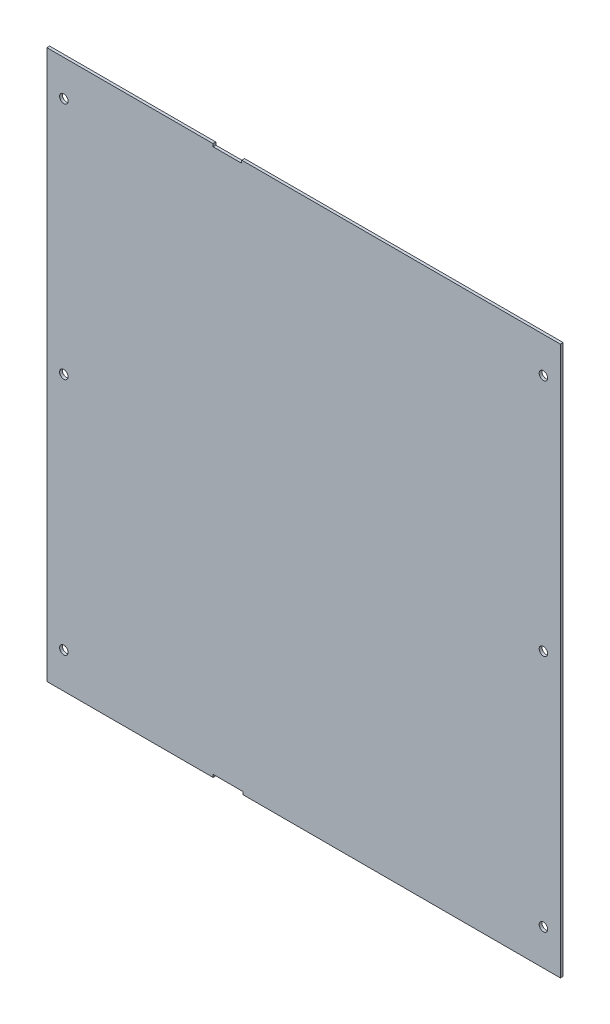
SolidWorks part; units mm, degrees
ref_plane "Front Plane" through (0, 0, 0) normal (0, 0, 1) x (1, 0, 0)
ref_plane "Top Plane" through (0, 0, 0) normal (0, 1, 0) x (1, 0, 0)
ref_plane "Right Plane" through (0, 0, 0) normal (1, 0, 0) x (0, 0, -1)
sketch "Sketch2" plane through (0, 0, 0) normal (0, 0, 1) x (1, 0, 0)
  line L0 (-66.4, 201.34) -> (-66.4, 199.34)
  line L1 (-188.4, 201.34) -> (-66.4, 201.34)
  line L2 (-188.4, 201.34) -> (-188.4, -201.34)
  line L3 (-188.4, -201.34) -> (-66.4, -201.34)
  line L4 (188.4, 201.34) -> (188.4, -201.34)
  line L5 (-188.4, 201.34) -> (188.4, -201.34) construction
  line L6 (-188.4, -201.34) -> (188.4, 201.34) construction
  line L7 (-66.4, 199.34) -> (-45.4, 199.34)
  line L8 (-45.4, 199.34) -> (-45.4, 201.34)
  line L9 (-45.4, 201.34) -> (188.4, 201.34)
  line L10 (-44.4, -201.34) -> (-44.4, -199.34)
  line L11 (-44.4, -199.34) -> (-66.4, -199.34)
  line L12 (-66.4, -199.34) -> (-66.4, -201.34)
  line L13 (-44.4, -201.34) -> (188.4, -201.34)
  point P0 (0, 0)
  dimension "D1" = 2
  dimension "Length 1" = 376.8
  dimension "D2" = 122
  dimension "Length 2" = 402.68
  dimension "D3" = 143
  dimension "D4" = 122
  dimension "D5" = 144
  dimension "D6" = 2
extrude "Boss-Extrude1" add sketch "Sketch2" along normal blind 2.032
sketch "Sketch3" [suppressed] plane through (0, 0, 2.032) normal (0, 0, 1) x (1, 0, 0)
  circle A0 centre (-175.117, 128.01) radius 3.1
  circle A1 centre (175.117, 128.01) radius 3.1
  circle A8 centre (-175.1171, -128.01) radius 3.1
  circle A9 centre (175.1169, -128.01) radius 3.1
  dimension "D1" = 6.2
extrude "Cut-Extrude1" [suppressed] cut sketch "Sketch3" against normal through all both and the other way through all
fillet "Fillet1" [suppressed] radius 10
sketch "Sketch4" [suppressed] plane through (0, 0, 0) normal (0, 0, -1) x (-1, 0, 0)
  circle A0 centre (-423.777, 128.01) radius 3.1
  circle A1 centre (423.777, 128.01) radius 3.1
  circle A2 centre (423.777, -128.01) radius 3.1
  circle A3 centre (-423.777, -128.01) radius 3.1
  dimension "D1" = 6.2
extrude "Cut-Extrude2" [suppressed] cut sketch "Sketch4" against normal through all both and the other way through all
sketch "Sketch5" [suppressed] plane through (0, 0, 0) normal (0, 0, -1) x (-1, 0, 0)
  circle A0 centre (-175.117, -437.5) radius 3.1
  circle A1 centre (175.1169, -437.5) radius 3.1
  circle A2 centre (175.1169, 437.5) radius 3.1
  circle A3 centre (-175.117, 437.5) radius 3.1
  dimension "D1" = 6.2
extrude "Cut-Extrude3" [suppressed] cut sketch "Sketch5" against normal through all both and the other way through all
fillet "Fillet3" [suppressed] radius 10
sketch "Sketch6" plane through (0, 0, 0) normal (0, 0, -1) x (-1, 0, 0)
  circle A0 centre (175.9, -175.117) radius 3.1
  circle A1 centre (175.9, 175.117) radius 3.1
  circle A2 centre (-175.9, 175.117) radius 3.1
  circle A3 centre (-175.9, -175.117) radius 3.1
  circle A5 centre (-175.9, 0) radius 3.1
  circle A6 centre (175.9, 0) radius 3.1
  dimension "D1" = 6.2
  dimension "D2" = 6.2
  dimension "D3" = 6.2
fillet "Fillet5" [suppressed] radius 10
extrude "Cut-Extrude4" cut sketch "Sketch6" against normal through all both and the other way through all
sketch "Sketch7" [suppressed] plane through (0, 0, 2.032) normal (0, 0, 1) x (1, 0, 0)
  circle A0 centre (-139.6, -129.6148) radius 3.1
  circle A1 centre (-139.6, 138.5552) radius 3.1
  circle A2 centre (139.6, 151.166) radius 3.1
  circle A3 centre (139.6, -129.36) radius 3.1
  dimension "D1" = 6.2
extrude "Cut-Extrude5" [suppressed] cut sketch "Sketch7" against normal through all both and the other way through all
fillet "Fillet4" [suppressed] radius 10
sketch "Sketch8" [suppressed] plane through (0, 0, 2.032) normal (0, 0, 1) x (1, 0, 0)
  line L0 (-37.3761, -47.01) -> (-37.3761, -22.01) construction
  line L1 (32.5, -51.886) -> (-32.5, -51.886) construction
  line L2 (37.376, -22.01) -> (37.376, -47.01) construction
  line L3 (-32.5, -17.1339) -> (32.5, -17.1339) construction
  line L4 (-37.3761, -47.01) -> (-37.3761, -22.01) construction
  line L5 (32.5, -51.886) -> (-32.5, -51.886) construction
  line L6 (37.376, -22.01) -> (37.376, -47.01) construction
  line L7 (-32.5, -17.1339) -> (32.5, -17.1339) construction
  line L8 (-37.6761, -47.01) -> (-37.6761, -22.01)
  line L9 (32.5, -52.186) -> (-32.5, -52.186)
  line L10 (37.676, -22.01) -> (37.676, -47.01)
  line L11 (-32.5, -16.8339) -> (32.5, -16.8339)
  arc A0 (-37.3761, -47.01) -> (-32.5, -51.886) centre (-32.5, -47.01) ccw construction
  arc A1 (32.5, -51.886) -> (37.376, -47.01) centre (32.5, -47.01) ccw construction
  arc A2 (37.376, -22.01) -> (32.5, -17.1339) centre (32.5, -22.01) ccw construction
  arc A3 (-32.5, -17.1339) -> (-37.3761, -22.01) centre (-32.5, -22.01) ccw construction
  arc A4 (-37.3761, -47.01) -> (-32.5, -51.886) centre (-32.5, -47.01) ccw construction
  arc A5 (32.5, -51.886) -> (37.376, -47.01) centre (32.5, -47.01) ccw construction
  arc A6 (37.376, -22.01) -> (32.5, -17.1339) centre (32.5, -22.01) ccw construction
  arc A7 (-32.5, -17.1339) -> (-37.3761, -22.01) centre (-32.5, -22.01) ccw construction
  arc A8 (-32.5, -16.8339) -> (-37.6761, -22.01) centre (-32.5, -22.01) ccw
  arc A9 (-37.6761, -47.01) -> (-32.5, -52.186) centre (-32.5, -47.01) ccw
  arc A10 (32.5, -52.186) -> (37.676, -47.01) centre (32.5, -47.01) ccw
  arc A11 (37.676, -22.01) -> (32.5, -16.8339) centre (32.5, -22.01) ccw
  dimension "D1" = 0.3
extrude "Cut-Extrude6" [suppressed] cut sketch "Sketch8" against normal through all
sketch "Sketch9" [suppressed] plane through (0, 0, 2.032) normal (0, 0, 1) x (1, 0, 0)
  line L0 (-51.9979, -76.9078) -> (-51.9979, -83.1078) construction
  line L1 (-48.8979, -76.9078) -> (-48.8979, -83.1078)
  line L2 (-55.0979, -76.9078) -> (-55.0979, -83.1078)
  line L3 (51.9978, -76.9078) -> (51.9978, -83.1078) construction
  line L4 (55.0978, -76.9078) -> (55.0978, -83.1078)
  line L5 (48.8978, -76.9078) -> (48.8978, -83.1078)
  circle A0 centre (-51.9979, -1.5121) radius 3.1
  circle A1 centre (51.9978, -1.5121) radius 3.1
  circle A2 centre (-51.9979, -80.0078) radius 3.1 construction
  arc A3 (-48.8979, -76.9078) -> (-55.0979, -76.9078) centre (-51.9979, -76.9078) ccw
  arc A4 (-55.0979, -83.1078) -> (-48.8979, -83.1078) centre (-51.9979, -83.1078) ccw
  circle A5 centre (51.9978, -80.0078) radius 3.1 construction
  arc A6 (55.0978, -76.9078) -> (48.8978, -76.9078) centre (51.9978, -76.9078) ccw
  arc A7 (48.8978, -83.1078) -> (55.0978, -83.1078) centre (51.9978, -83.1078) ccw
  point P11 (-51.9979, -80.0078)
  point P17 (51.9978, -80.0078)
  dimension "D1" = 6.2
extrude "Cut-Extrude7" [suppressed] cut sketch "Sketch9" against normal through all
sketch "Sketch10" [suppressed] plane through (0, 0, 2.032) normal (0, 0, 1) x (1, 0, 0)
  line L0 (90, 90.8143) -> (-90, 90.8143) construction
  line L1 (75.5, 121.0648) -> (-75.5, 121.0648) construction
  line L2 (75.5, 90.8143) -> (-75.5, 90.8143) construction
  line L3 (75.5, 121.0648) -> (-75.5, 121.0648) construction
  line L4 (75.5, 90.5143) -> (-75.5, 90.5143)
  line L5 (75.5, 121.3648) -> (-75.5, 121.3648)
  spline S0 degree 3 poles (3074.5134, 128.3274) (69.9947, 120.8875) (74.4296, 121.0676) (75.5298, 121.0647) (75.5326, 121.0647) (75.6464, 121.0643) (75.8632, 121.0597) (76.1642, 121.0437) (76.381, 121.0257) (76.5878, 121.0048) (76.7942, 120.9803) (77.0603, 120.9413) (77.3248, 120.8952) (77.5598, 120.8477) (77.7949, 120.7947) (77.9818, 120.7481) (78.1109, 120.7132) (78.2822, 120.6658) (78.5457, 120.5872) (78.9382, 120.4526) (79.2301, 120.3392) (79.3912, 120.2721) (79.5867, 120.1894) (79.8287, 120.0797) (80.0659, 119.9615) (80.3074, 119.8374) (80.4668, 119.7503) (80.8016, 119.5566) (81.1538, 119.3396) (81.5223, 119.0841) (81.7178, 118.9395) (81.8836, 118.8158) (82.0678, 118.6719) (82.2476, 118.5231) (82.4279, 118.3716) (82.5907, 118.2288) (82.7493, 118.0824) (82.9322, 117.9119) (83.2327, 117.6176) (83.6639, 117.1527) (83.9602, 116.8013) (84.1153, 116.6069) (84.2773, 116.4024) (84.4141, 116.2207) (84.6783, 115.8519) (84.9333, 115.4777) (85.2917, 114.8964) (85.6175, 114.311) (85.8168, 113.9147) (86.0153, 113.4997) (86.199, 113.0919) (86.3667, 112.6759) (86.5131, 112.2932) (86.6057, 112.0372) (86.6922, 111.7793) (86.7672, 111.5516) (86.8201, 111.3823) (86.9423, 110.9692) (87.0765, 110.4773) (87.247, 109.7286) (87.3625, 109.1005) (87.4598, 108.4609) (87.5282, 107.8937) (87.5661, 107.4468) (87.5939, 107.0493) (87.6148, 106.6536) (87.6234, 106.2582) (87.6251, 106.0243) (87.6252, 105.9711) (87.6249, 105.6521) (87.6131, 105.121) (87.5623, 104.3289) (87.4962, 103.7081) (87.4136, 103.0987) (87.3259, 102.565) (87.2377, 102.1278) (87.1497, 101.7237) (87.0462, 101.2874) (86.9261, 100.8539) (86.8399, 100.5642) (86.8173, 100.4902) (86.7193, 100.1763) (86.5601, 99.7025) (86.2936, 99.0104) (86.0691, 98.4959) (85.9353, 98.2118) (85.8046, 97.939) (85.5968, 97.5281) (85.2615, 96.9315) (84.9154, 96.3749) (84.674, 96.0215) (84.4707, 95.7372) (84.3836, 95.6191) (84.1969, 95.3742) (84.0085, 95.1357) (83.8127, 94.9039) (83.5714, 94.6273) (83.2684, 94.2969) (82.801, 93.8368) (82.325, 93.4136) (81.9762, 93.1336) (81.7857, 92.9898) (81.6442, 92.8839) (81.4108, 92.7157) (81.0521, 92.477) (80.7023, 92.2626) (80.4711, 92.1321) (80.188, 91.9784) (79.8408, 91.802) (79.3125, 91.5689) (78.7817, 91.3682) (78.4002, 91.2473) (78.1974, 91.1898) (78.1177, 91.1676) (77.9122, 91.1121) (77.5556, 91.0277) (77.1709, 90.9552) (76.9362, 90.9195) (76.822, 90.9037) (76.7327, 90.8917) (76.589, 90.8744) (76.4218, 90.8572) (76.2707, 90.8443) (76.119, 90.8335) (75.9751, 90.8254) (75.8173, 90.819) (75.6699, 90.8154) (75.5675, 90.8144) (75.515, 90.8143) (75.5096, 90.8143) (74.905, 90.8139) (86.1929, 90.8711) (3073.38, 91.1293) knots -0.002735 -0.002735 -0.002735 -0.002735 0.000024 0.000024 0.000031 0.000031 0.00032 0.000611 0.000881 0.000959 0.001235 0.001516 0.001798 0.002081 0.002271 0.00255 0.002673 0.002673 0.003081 0.003491 0.003902 0.004009 0.004009 0.004534 0.004802 0.004802 0.005346 0.005346 0.00596 0.006584 0.006682 0.006682 0.007198 0.007375 0.007375 0.007897 0.008019 0.008019 0.008644 0.009276 0.009915 0.010016 0.010016 0.010692 0.010692 0.01136 0.012037 0.01273 0.013365 0.013365 0.014106 0.014701 0.014701 0.015325 0.01551 0.01551 0.016038 0.016038 0.016796 0.017562 0.018339 0.018711 0.0195 0.020047 0.020047 0.020686 0.021225 0.021225 0.021384 0.021384 0.022179 0.022975 0.023768 0.024057 0.024824 0.025393 0.025393 0.026061 0.026729 0.026729 0.02696 0.02696 0.027709 0.028454 0.029189 0.029402 0.029402 0.030103 0.030794 0.031468 0.032075 0.032075 0.032512 0.032512 0.032989 0.033412 0.033412 0.03408 0.034748 0.035373 0.035987 0.036085 0.036085 0.036513 0.036938 0.037359 0.037729 0.037729 0.03832 0.038894 0.039463 0.040026 0.040094 0.040094 0.040274 0.04073 0.041182 0.041431 0.041431 0.041522 0.041701 0.041881 0.04206 0.042186 0.042356 0.042495 0.042636 0.042751 0.042751 0.042763 0.042763 0.04424 0.04424 0.04424 0.04424 weights 1 1 1 1 1 1 1 1 1 1 1 1 1 1 1 1 1 1 1 1 1 1 1 1 1 1 1 1 1 1 1 1 1 1 1 1 1 1 1 1 1 1 1 1 1 1 1 1 1 1 1 1 1 1 1 1 1 1 1 1 1 1 1 1 1 1 1 1 1 1 1 1 1 1 1 1 1 1 1 1 1 1 1 1 1 1 1 1 1 1 1 1 1 1 1 1 1 1 1 1 1 1 1 1 1 1 1 1 1 1 1 1 1 1 1 1 1 1 1 1 1 1 1 1 1 1 1 1 1 1 1 1 1 only from (75.5, 121.0648) to (75.5, 90.8143) construction
  spline S1 degree 3 poles (-3073.3122, 91.0618) (-68.1123, 90.8701) (-74.8748, 90.8132) (-75.5178, 90.8143) (-75.5188, 90.8143) (-75.6217, 90.8145) (-75.8102, 90.8179) (-76.0955, 90.831) (-76.3619, 90.851) (-76.5858, 90.8739) (-76.7898, 90.8988) (-76.9915, 90.9272) (-77.2231, 90.9655) (-77.4535, 91.0092) (-77.6838, 91.0585) (-77.9135, 91.1133) (-78.0691, 91.1542) (-78.2957, 91.2169) (-78.5939, 91.3066) (-79.0185, 91.4558) (-79.292, 91.5651) (-79.5791, 91.6863) (-79.8887, 91.8262) (-80.19, 91.98) (-80.431, 92.1099) (-80.5257, 92.1628) (-80.8023, 92.3227) (-81.1645, 92.5459) (-81.531, 92.801) (-81.7204, 92.9414) (-81.86, 93.0454) (-82.1004, 93.2319) (-82.4461, 93.5213) (-82.6659, 93.719) (-82.9234, 93.9587) (-83.2202, 94.2488) (-83.646, 94.7063) (-83.9884, 95.1104) (-84.1878, 95.3632) (-84.3522, 95.5769) (-84.4471, 95.7045) (-84.6398, 95.973) (-84.836, 96.257) (-85.0675, 96.6184) (-85.2256, 96.8798) (-85.2925, 96.9937) (-85.434, 97.2372) (-85.6646, 97.6556) (-85.9851, 98.3049) (-86.2393, 98.8843) (-86.3829, 99.2453) (-86.4494, 99.4187) (-86.55, 99.6841) (-86.6603, 99.9986) (-86.7491, 100.2733) (-86.796, 100.4205) (-86.8377, 100.5557) (-86.8778, 100.6914) (-86.9586, 100.968) (-87.0905, 101.4582) (-87.2577, 102.2029) (-87.3631, 102.7847) (-87.4242, 103.1837) (-87.4447, 103.3291) (-87.4978, 103.7198) (-87.5689, 104.3709) (-87.6172, 105.2208) (-87.6253, 105.7445) (-87.6253, 105.9682) (-87.6252, 105.997) (-87.6239, 106.2925) (-87.6102, 106.8253) (-87.5586, 107.5863) (-87.4824, 108.2948) (-87.3824, 108.9904) (-87.2522, 109.7032) (-87.0975, 110.3876) (-86.9658, 110.8838) (-86.8849, 111.1642) (-86.8565, 111.2593) (-86.8202, 111.38) (-86.7924, 111.4698) (-86.7084, 111.7335) (-86.617, 112.0056) (-86.5018, 112.3221) (-86.4473, 112.4659) (-86.3387, 112.7484) (-86.1745, 113.1489) (-85.9253, 113.6947) (-85.6673, 114.2147) (-85.3669, 114.7671) (-85.0165, 115.3478) (-84.7388, 115.7647) (-84.5819, 115.9866) (-84.4547, 116.1642) (-84.3562, 116.297) (-84.1525, 116.5617) (-83.9899, 116.7652) (-83.8222, 116.9634) (-83.7278, 117.0727) (-83.6931, 117.1124) (-83.512, 117.3171) (-83.2145, 117.6374) (-82.7539, 118.0859) (-82.3108, 118.4763) (-81.9806, 118.7415) (-81.7867, 118.8888) (-81.7261, 118.9339) (-81.5923, 119.0328) (-81.36, 119.1984) (-81.006, 119.4314) (-80.7579, 119.5818) (-80.6329, 119.6543) (-80.5302, 119.7137) (-80.4331, 119.768) (-80.1632, 119.9135) (-79.8189, 120.0873) (-79.2869, 120.3208) (-78.7504, 120.5219) (-78.374, 120.6396) (-78.1216, 120.7105) (-77.9102, 120.7674) (-77.5659, 120.8488) (-77.1858, 120.9214) (-76.9471, 120.958) (-76.8184, 120.9759) (-76.7272, 120.988) (-76.582, 121.0054) (-76.4149, 121.0225) (-76.2649, 121.0352) (-76.1143, 121.0458) (-75.972, 121.0538) (-75.8151, 121.0601) (-75.6689, 121.0637) (-75.5671, 121.0646) (-75.515, 121.0648) (-75.5096, 121.0648) (-74.9079, 121.0651) (-86.2343, 121.0084) (-3073.1531, 120.7526) knots -0.001473 -0.001473 -0.001473 -0.001473 0.000013 0.000013 0.000016 0.000016 0.000262 0.000488 0.000778 0.001021 0.001162 0.001413 0.001666 0.001921 0.002175 0.002427 0.002667 0.002667 0.00313 0.003594 0.004001 0.004001 0.004517 0.00501 0.00501 0.005334 0.005334 0.005966 0.006608 0.006668 0.006668 0.007126 0.007571 0.008002 0.008002 0.008616 0.009237 0.009867 0.010196 0.010196 0.010669 0.010669 0.011178 0.011692 0.011939 0.012084 0.012084 0.012777 0.013509 0.014247 0.014667 0.014667 0.0148 0.015513 0.015656 0.015656 0.015971 0.016076 0.016076 0.016826 0.017586 0.018355 0.018595 0.018795 0.018795 0.019775 0.020751 0.02133 0.02133 0.021415 0.021415 0.022207 0.023001 0.023696 0.024344 0.025112 0.025872 0.026446 0.026646 0.026742 0.026742 0.027021 0.027021 0.027563 0.027871 0.02802 0.02802 0.028771 0.029311 0.029815 0.03051 0.031195 0.031844 0.032003 0.032003 0.032493 0.032493 0.032991 0.033263 0.033263 0.033421 0.033421 0.034077 0.034725 0.035343 0.035843 0.035988 0.036067 0.036067 0.036482 0.036912 0.037319 0.037341 0.037341 0.037673 0.037673 0.038257 0.038828 0.039418 0.039978 0.040009 0.040201 0.04063 0.041056 0.041342 0.041342 0.04144 0.041618 0.041798 0.041977 0.042099 0.042269 0.042405 0.042545 0.04266 0.04266 0.042671 0.042671 0.044141 0.044141 0.044141 0.044141 weights 1 1 1 1 1 1 1 1 1 1 1 1 1 1 1 1 1 1 1 1 1 1 1 1 1 1 1 1 1 1 1 1 1 1 1 1 1 1 1 1 1 1 1 1 1 1 1 1 1 1 1 1 1 1 1 1 1 1 1 1 1 1 1 1 1 1 1 1 1 1 1 1 1 1 1 1 1 1 1 1 1 1 1 1 1 1 1 1 1 1 1 1 1 1 1 1 1 1 1 1 1 1 1 1 1 1 1 1 1 1 1 1 1 1 1 1 1 1 1 1 1 1 1 1 1 1 1 1 1 1 1 1 1 1 1 1 1 1 1 1 only from (-75.5, 90.8143) to (-75.5, 121.0648) construction
  spline S2 degree 3 poles (75.5, 121.0648) (75.5079, 121.0648) (75.5205, 121.0647) (75.5326, 121.0647) (75.6464, 121.0643) (75.8632, 121.0597) (76.1642, 121.0437) (76.381, 121.0257) (76.5878, 121.0048) (76.7942, 120.9803) (77.0603, 120.9413) (77.3248, 120.8952) (77.5598, 120.8477) (77.7949, 120.7947) (77.9818, 120.7481) (78.1109, 120.7132) (78.2822, 120.6658) (78.5457, 120.5872) (78.9382, 120.4526) (79.2301, 120.3392) (79.3912, 120.2721) (79.5867, 120.1894) (79.8287, 120.0797) (80.0659, 119.9615) (80.3074, 119.8374) (80.4668, 119.7503) (80.8016, 119.5566) (81.1538, 119.3396) (81.5223, 119.0841) (81.7178, 118.9395) (81.8836, 118.8158) (82.0678, 118.6719) (82.2476, 118.5231) (82.4279, 118.3716) (82.5907, 118.2288) (82.7493, 118.0824) (82.9322, 117.9119) (83.2327, 117.6176) (83.6639, 117.1527) (83.9602, 116.8013) (84.1153, 116.6069) (84.2773, 116.4024) (84.4141, 116.2207) (84.6783, 115.8519) (84.9333, 115.4777) (85.2917, 114.8964) (85.6175, 114.311) (85.8168, 113.9147) (86.0153, 113.4997) (86.199, 113.0919) (86.3667, 112.6759) (86.5131, 112.2932) (86.6057, 112.0372) (86.6922, 111.7793) (86.7672, 111.5516) (86.8201, 111.3823) (86.9423, 110.9692) (87.0765, 110.4773) (87.247, 109.7286) (87.3625, 109.1005) (87.4598, 108.4609) (87.5282, 107.8937) (87.5661, 107.4468) (87.5939, 107.0493) (87.6148, 106.6536) (87.6234, 106.2582) (87.6251, 106.0243) (87.6252, 105.9711) (87.6249, 105.6521) (87.6131, 105.121) (87.5623, 104.3289) (87.4962, 103.7081) (87.4136, 103.0987) (87.3259, 102.565) (87.2377, 102.1278) (87.1497, 101.7237) (87.0462, 101.2874) (86.9261, 100.8539) (86.8399, 100.5642) (86.8173, 100.4902) (86.7193, 100.1763) (86.5601, 99.7025) (86.2936, 99.0104) (86.0691, 98.4959) (85.9353, 98.2118) (85.8046, 97.939) (85.5968, 97.5281) (85.2615, 96.9315) (84.9154, 96.3749) (84.674, 96.0215) (84.4707, 95.7372) (84.3836, 95.6191) (84.1969, 95.3742) (84.0085, 95.1357) (83.8127, 94.9039) (83.5714, 94.6273) (83.2684, 94.2969) (82.801, 93.8368) (82.325, 93.4136) (81.9762, 93.1336) (81.7857, 92.9898) (81.6442, 92.8839) (81.4108, 92.7157) (81.0521, 92.477) (80.7023, 92.2626) (80.4711, 92.1321) (80.188, 91.9784) (79.8408, 91.802) (79.3125, 91.5689) (78.7817, 91.3682) (78.4002, 91.2473) (78.1974, 91.1898) (78.1177, 91.1676) (77.9122, 91.1121) (77.5556, 91.0277) (77.1709, 90.9552) (76.9362, 90.9195) (76.822, 90.9037) (76.7327, 90.8917) (76.589, 90.8744) (76.4218, 90.8572) (76.2707, 90.8443) (76.119, 90.8335) (75.9751, 90.8254) (75.8173, 90.819) (75.6699, 90.8154) (75.5675, 90.8144) (75.515, 90.8143) (75.5076, 90.8143) (75.5015, 90.8143) (75.5, 90.8143) knots 0 0 0 0 0.000024 0.000031 0.000031 0.00032 0.000611 0.000881 0.000959 0.001235 0.001516 0.001798 0.002081 0.002271 0.00255 0.002673 0.002673 0.003081 0.003491 0.003902 0.004009 0.004009 0.004534 0.004802 0.004802 0.005346 0.005346 0.00596 0.006584 0.006682 0.006682 0.007198 0.007375 0.007375 0.007897 0.008019 0.008019 0.008644 0.009276 0.009915 0.010016 0.010016 0.010692 0.010692 0.01136 0.012037 0.01273 0.013365 0.013365 0.014106 0.014701 0.014701 0.015325 0.01551 0.01551 0.016038 0.016038 0.016796 0.017562 0.018339 0.018711 0.0195 0.020047 0.020047 0.020686 0.021225 0.021225 0.021384 0.021384 0.022179 0.022975 0.023768 0.024057 0.024824 0.025393 0.025393 0.026061 0.026729 0.026729 0.02696 0.02696 0.027709 0.028454 0.029189 0.029402 0.029402 0.030103 0.030794 0.031468 0.032075 0.032075 0.032512 0.032512 0.032989 0.033412 0.033412 0.03408 0.034748 0.035373 0.035987 0.036085 0.036085 0.036513 0.036938 0.037359 0.037729 0.037729 0.03832 0.038894 0.039463 0.040026 0.040094 0.040094 0.040274 0.04073 0.041182 0.041431 0.041431 0.041522 0.041701 0.041881 0.04206 0.042186 0.042356 0.042495 0.042636 0.042751 0.042751 0.042763 0.042767 0.042767 0.042767 0.042767 weights 1 1 1 1 1 1 1 1 1 1 1 1 1 1 1 1 1 1 1 1 1 1 1 1 1 1 1 1 1 1 1 1 1 1 1 1 1 1 1 1 1 1 1 1 1 1 1 1 1 1 1 1 1 1 1 1 1 1 1 1 1 1 1 1 1 1 1 1 1 1 1 1 1 1 1 1 1 1 1 1 1 1 1 1 1 1 1 1 1 1 1 1 1 1 1 1 1 1 1 1 1 1 1 1 1 1 1 1 1 1 1 1 1 1 1 1 1 1 1 1 1 1 1 1 1 1 1 1 1 1 1 construction
  spline S3 degree 3 poles (-75.5, 90.8143) (-75.5046, 90.8143) (-75.512, 90.8143) (-75.5188, 90.8143) (-75.6217, 90.8145) (-75.8102, 90.8179) (-76.0955, 90.831) (-76.3619, 90.851) (-76.5858, 90.8739) (-76.7898, 90.8988) (-76.9915, 90.9272) (-77.2231, 90.9655) (-77.4535, 91.0092) (-77.6838, 91.0585) (-77.9135, 91.1133) (-78.0691, 91.1542) (-78.2957, 91.2169) (-78.5939, 91.3066) (-79.0185, 91.4558) (-79.292, 91.5651) (-79.5791, 91.6863) (-79.8887, 91.8262) (-80.19, 91.98) (-80.431, 92.1099) (-80.5257, 92.1628) (-80.8023, 92.3227) (-81.1645, 92.5459) (-81.531, 92.801) (-81.7204, 92.9414) (-81.86, 93.0454) (-82.1004, 93.2319) (-82.4461, 93.5213) (-82.6659, 93.719) (-82.9234, 93.9587) (-83.2202, 94.2488) (-83.646, 94.7063) (-83.9884, 95.1104) (-84.1878, 95.3632) (-84.3522, 95.5769) (-84.4471, 95.7045) (-84.6398, 95.973) (-84.836, 96.257) (-85.0675, 96.6184) (-85.2256, 96.8798) (-85.2925, 96.9937) (-85.434, 97.2372) (-85.6646, 97.6556) (-85.9851, 98.3049) (-86.2393, 98.8843) (-86.3829, 99.2453) (-86.4494, 99.4187) (-86.55, 99.6841) (-86.6603, 99.9986) (-86.7491, 100.2733) (-86.796, 100.4205) (-86.8377, 100.5557) (-86.8778, 100.6914) (-86.9586, 100.968) (-87.0905, 101.4582) (-87.2577, 102.2029) (-87.3631, 102.7847) (-87.4242, 103.1837) (-87.4447, 103.3291) (-87.4978, 103.7198) (-87.5689, 104.3709) (-87.6172, 105.2208) (-87.6253, 105.7445) (-87.6253, 105.9682) (-87.6252, 105.997) (-87.6239, 106.2925) (-87.6102, 106.8253) (-87.5586, 107.5863) (-87.4824, 108.2948) (-87.3824, 108.9904) (-87.2522, 109.7032) (-87.0975, 110.3876) (-86.9658, 110.8838) (-86.8849, 111.1642) (-86.8565, 111.2593) (-86.8202, 111.38) (-86.7924, 111.4698) (-86.7084, 111.7335) (-86.617, 112.0056) (-86.5018, 112.3221) (-86.4473, 112.4659) (-86.3387, 112.7484) (-86.1745, 113.1489) (-85.9253, 113.6947) (-85.6673, 114.2147) (-85.3669, 114.7671) (-85.0165, 115.3478) (-84.7388, 115.7647) (-84.5819, 115.9866) (-84.4547, 116.1642) (-84.3562, 116.297) (-84.1525, 116.5617) (-83.9899, 116.7652) (-83.8222, 116.9634) (-83.7278, 117.0727) (-83.6931, 117.1124) (-83.512, 117.3171) (-83.2145, 117.6374) (-82.7539, 118.0859) (-82.3108, 118.4763) (-81.9806, 118.7415) (-81.7867, 118.8888) (-81.7261, 118.9339) (-81.5923, 119.0328) (-81.36, 119.1984) (-81.006, 119.4314) (-80.7579, 119.5818) (-80.6329, 119.6543) (-80.5302, 119.7137) (-80.4331, 119.768) (-80.1632, 119.9135) (-79.8189, 120.0873) (-79.2869, 120.3208) (-78.7504, 120.5219) (-78.374, 120.6396) (-78.1216, 120.7105) (-77.9102, 120.7674) (-77.5659, 120.8488) (-77.1858, 120.9214) (-76.9471, 120.958) (-76.8184, 120.9759) (-76.7272, 120.988) (-76.582, 121.0054) (-76.4149, 121.0225) (-76.2649, 121.0352) (-76.1143, 121.0458) (-75.972, 121.0538) (-75.8151, 121.0601) (-75.6689, 121.0637) (-75.5671, 121.0646) (-75.515, 121.0648) (-75.5076, 121.0648) (-75.5015, 121.0648) (-75.5, 121.0648) knots 0 0 0 0 0.000013 0.000016 0.000016 0.000262 0.000488 0.000778 0.001021 0.001162 0.001413 0.001666 0.001921 0.002175 0.002427 0.002667 0.002667 0.00313 0.003594 0.004001 0.004001 0.004517 0.00501 0.00501 0.005334 0.005334 0.005966 0.006608 0.006668 0.006668 0.007126 0.007571 0.008002 0.008002 0.008616 0.009237 0.009867 0.010196 0.010196 0.010669 0.010669 0.011178 0.011692 0.011939 0.012084 0.012084 0.012777 0.013509 0.014247 0.014667 0.014667 0.0148 0.015513 0.015656 0.015656 0.015971 0.016076 0.016076 0.016826 0.017586 0.018355 0.018595 0.018795 0.018795 0.019775 0.020751 0.02133 0.02133 0.021415 0.021415 0.022207 0.023001 0.023696 0.024344 0.025112 0.025872 0.026446 0.026646 0.026742 0.026742 0.027021 0.027021 0.027563 0.027871 0.02802 0.02802 0.028771 0.029311 0.029815 0.03051 0.031195 0.031844 0.032003 0.032003 0.032493 0.032493 0.032991 0.033263 0.033263 0.033421 0.033421 0.034077 0.034725 0.035343 0.035843 0.035988 0.036067 0.036067 0.036482 0.036912 0.037319 0.037341 0.037341 0.037673 0.037673 0.038257 0.038828 0.039418 0.039978 0.040009 0.040201 0.04063 0.041056 0.041342 0.041342 0.04144 0.041618 0.041798 0.041977 0.042099 0.042269 0.042405 0.042545 0.04266 0.04266 0.042671 0.042676 0.042676 0.042676 0.042676 weights 1 1 1 1 1 1 1 1 1 1 1 1 1 1 1 1 1 1 1 1 1 1 1 1 1 1 1 1 1 1 1 1 1 1 1 1 1 1 1 1 1 1 1 1 1 1 1 1 1 1 1 1 1 1 1 1 1 1 1 1 1 1 1 1 1 1 1 1 1 1 1 1 1 1 1 1 1 1 1 1 1 1 1 1 1 1 1 1 1 1 1 1 1 1 1 1 1 1 1 1 1 1 1 1 1 1 1 1 1 1 1 1 1 1 1 1 1 1 1 1 1 1 1 1 1 1 1 1 1 1 1 1 1 1 1 1 1 1 construction
  spline S4 degree 1 poles (-75.5, 90.5143) (-75.5, 121.3648) knots 0 0 1 1 construction
  spline S5 degree 1 poles (75.5, 121.3648) (75.5, 90.5143) knots 0 0 1 1 construction
  spline S6 degree 3 poles (-75.5, 90.5143) (-75.6364, 90.5143) (-75.9178, 90.5203) (-76.4106, 90.5505) (-76.9682, 90.6146) (-77.583, 90.724) (-78.4367, 90.929) (-79.5539, 91.3171) (-81.1922, 92.1383) (-83.046, 93.5297) (-85.4559, 96.3039) (-87.4217, 100.5003) (-88.1781, 105.9528) (-87.4175, 111.3767) (-85.4702, 115.556) (-83.3502, 117.9986) (-81.9517, 119.1724) (-80.7872, 119.944) (-79.56, 120.5575) (-78.4813, 120.9369) (-77.5849, 121.1564) (-77.0009, 121.2574) (-76.5584, 121.3109) (-76.2401, 121.3392) (-75.9079, 121.3589) (-75.6314, 121.3648) (-75.5, 121.3648) knots 0 0 0 0 0.000333 0.000667 0.001334 0.002 0.002667 0.004001 0.005334 0.008002 0.010669 0.016003 0.021338 0.026672 0.032007 0.034674 0.036008 0.037341 0.038675 0.040009 0.040675 0.041342 0.041676 0.042009 0.042342 0.042676 0.042676 0.042676 0.042676
  spline S7 degree 3 poles (75.5, 121.3648) (75.7505, 121.3647) (76.2699, 121.3441) (76.935, 121.2693) (77.5771, 121.1569) (78.4459, 120.9475) (79.5593, 120.5593) (81.1959, 119.7385) (83.0542, 118.3419) (85.4627, 115.5649) (87.0341, 112.198) (87.7984, 108.6558) (87.9891, 105.9096) (87.7964, 103.2116) (87.0182, 99.6349) (85.4812, 96.3435) (83.3563, 93.8861) (81.9584, 92.712) (80.7938, 91.9388) (79.5626, 91.3225) (78.483, 90.9427) (77.5871, 90.7231) (77.0029, 90.622) (76.5596, 90.5682) (76.2408, 90.5399) (75.9082, 90.5202) (75.6315, 90.5143) (75.5, 90.5143) knots 0 0 0 0 0.000668 0.001336 0.002005 0.002673 0.004009 0.005346 0.008019 0.010692 0.016038 0.018711 0.021384 0.024056 0.026729 0.032075 0.034748 0.036085 0.037421 0.038758 0.040094 0.040762 0.041431 0.041765 0.042099 0.042433 0.042767 0.042767 0.042767 0.042767
  dimension "D1" = 0.3
extrude "Cut-Extrude8" [suppressed] cut sketch "Sketch10" against normal through all
sketch "Sketch11" [suppressed] plane through (0, 0, 2.032) normal (0, 0, 1) x (1, 0, 0)
